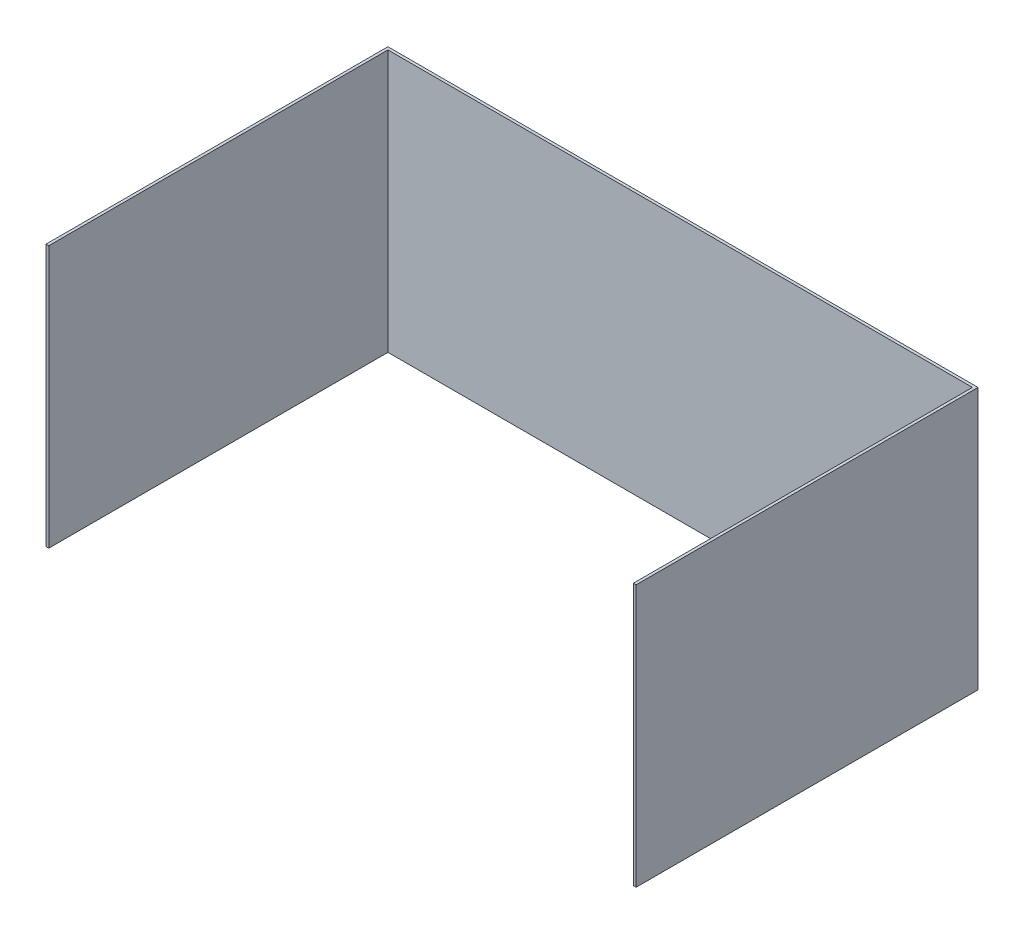
SolidWorks part; units mm, degrees
ref_plane "Front Plane" through (0, 0, 0) normal (0, 0, 1) x (1, 0, 0)
ref_plane "Top Plane" through (0, 0, 0) normal (0, 1, 0) x (1, 0, 0)
ref_plane "Right Plane" through (0, 0, 0) normal (1, 0, 0) x (0, 0, -1)
sketch "Sketch1" plane through (0, 0, 0) normal (0, 1, 0) x (1, 0, 0)
  line L2 (-339.725, -196.85) -> (-339.725, 196.85)
  line L3 (-339.725, 196.85) -> (339.725, 196.85)
  line L4 (339.725, -196.85) -> (339.725, 196.85)
  line L5 (-339.725, -196.85) -> (339.725, 196.85) construction
  line L6 (-339.725, 196.85) -> (339.725, -196.85) construction
  point P0 (0, 0)
  dimension "D1" = 679.45
  dimension "D2" = 393.7
extrude "Extrude-Thin1" add sketch "Sketch1" along normal blind 301.625 thin thin type one direction reverse wall 3.175
